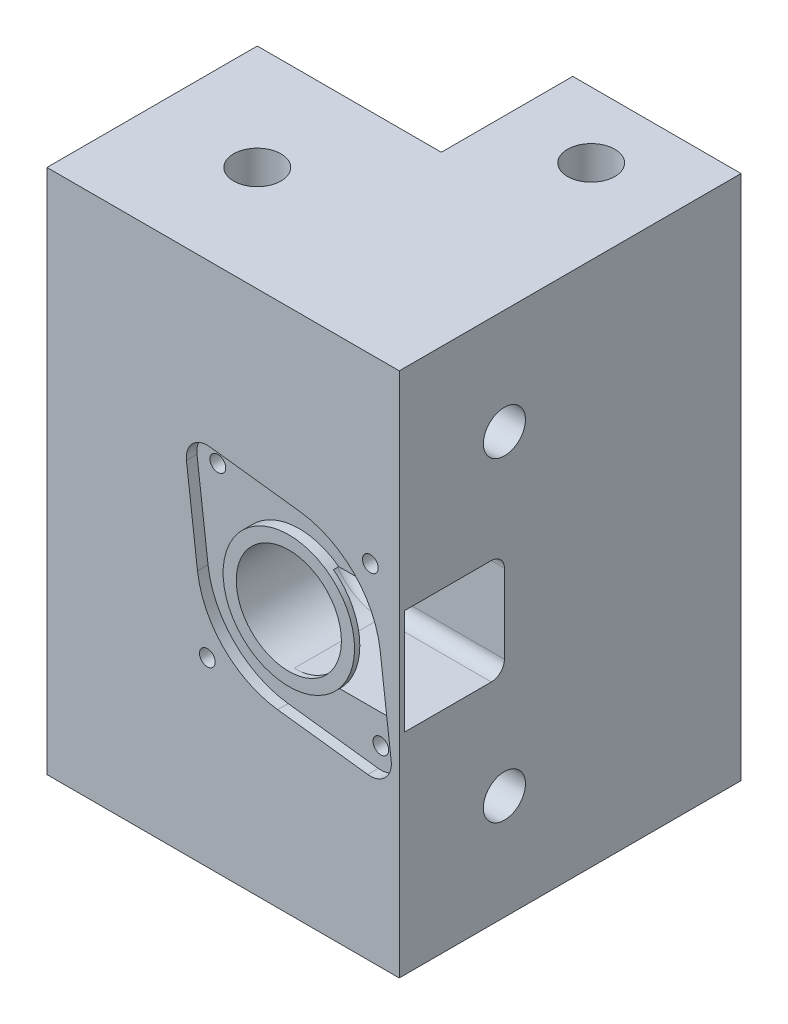
SolidWorks part; units mm, degrees
ref_plane "Front Plane" through (0, 0, 0) normal (0, 0, 1) x (1, 0, 0)
ref_plane "Top Plane" through (0, 0, 0) normal (0, 1, 0) x (1, 0, 0)
ref_plane "Right Plane" through (0, 0, 0) normal (1, 0, 0) x (0, 0, -1)
sketch "Sketch1" plane through (0, 0, 0) normal (0, 1, 0) x (1, 0, 0)
  line L19 (0, -40) -> (0, 0) construction
  line L24 (-25, 0) -> (-5, -40) construction
  line L25 (0, 25) -> (-25, 25) construction
  line L26 (-25, 25) -> (-25, 0) construction
  line L27 (0, 25) -> (32, 0) construction
  line L28 (32, 0) -> (0, 0) construction
  line L29 (-35, 0) -> (0, 0)
  line L30 (-35, -40) -> (-35, 0)
  line L31 (32, -40) -> (-35, -40)
  line L32 (32, 25) -> (32, -40)
  line L33 (0, 25) -> (32, 25)
  line L34 (0, 0) -> (0, 25)
  line L35 (-5, 5) -> (-5, -40) construction
  line L36 (-25, 25) -> (-5, 25) construction
  line L37 (-25, 25) -> (-25, 5) construction
  line L38 (-25, 5) -> (-5, 5) construction
  line L39 (-5, 25) -> (-5, 5) construction
  line L40 (16, 12.5) -> (-5, 22.5) construction
  line L41 (-25, 2.5) -> (-5, 2.5) construction
  line L42 (-25, 2.5) -> (-25, 22.5) construction
  line L43 (-25, 22.5) -> (-5, 22.5) construction
  line L44 (-5, 2.5) -> (-5, 22.5) construction
  line L45 (-25, 2.5) -> (-5, 22.5) construction
  line L46 (-25, 22.5) -> (-5, 2.5) construction
  line L47 (16, 12.5) -> (-5, 2.5) construction
  circle A10 centre (-15, -20) radius 16 construction
  circle A11 centre (-15, -20) radius 6.75 construction
  circle A12 centre (16, 12.5) radius 6 construction
  circle A13 centre (16, 12.5) radius 11 construction
  circle A14 centre (-15, -20) radius 4.5
  circle A15 centre (16, 12.5) radius 4.5
  point P1 (-15, 12.5)
  dimension "D4" = 40
  dimension "D6" = 9
  dimension "D3" = 32
  dimension "D5" = 20
  dimension "D7" = 13.5
  dimension "D8" = 32
  dimension "D9" = 9
  dimension "D10" = 12
  dimension "D11" = 22
  dimension "D1" = 25
  dimension "D2" = 25
  dimension "D12" = 20
extrude "Boss-Extrude1" add sketch "Sketch1" along normal blind 100
sketch "Sketch4" plane through (0, 0, 0) normal (0, -1, 0) x (-1, 0, 0)
  point P0 (15, -20)
hole_wizard "CBORE for M5 Hex Head Bolt2" positions "Sketch4" profile "Sketch5" counterbore size "M5" standard "ANSI Metric"
sketch "Sketch5" plane through (-15, 0, 20) normal (1, 0, 0) x (0, 0, -1)
  line L0 (0, 0) -> (0, 23.85)
  line L1 (0, 23.85) -> (6.75, 23.85)
  line L2 (6.75, 23.85) -> (6.75, 5)
  line L3 (6.75, 5) -> (16, 5)
  line L4 (16, 5) -> (16, 0)
  line L5 (16, 0) -> (0, 0)
  line L10 (0, 23.85) -> (-6.75, 23.85) construction
  line L11 (0, -6.35) -> (0, 107.95) construction
  dimension "Hole Dia." = 13.5
  dimension "Hole Depth" = 23.85
  dimension "C'Bore Dia." = 32
  dimension "C'Bore Depth" = 5
  dimension "Drill Angle" = 180
sketch "Sketch6" plane through (0, 0, 0) normal (0, -1, 0) x (-1, 0, 0)
  point P0 (-16, 12.5)
hole_wizard "CBORE for M5 Hex Head Bolt3" positions "Sketch6" profile "Sketch7" counterbore size "M5" standard "ANSI Metric"
sketch "Sketch7" plane through (16, 0, -12.5) normal (1, 0, 0) x (0, 0, -1)
  line L0 (0, 0) -> (0, 13.5)
  line L1 (0, 13.5) -> (5.1, 13.5)
  line L2 (5.1, 13.5) -> (5.1, 3.5)
  line L3 (5.1, 3.5) -> (11, 3.5)
  line L4 (11, 3.5) -> (11, 0)
  line L5 (11, 0) -> (0, 0)
  line L10 (0, 13.5) -> (-5.1, 13.5) construction
  line L11 (0, -6.35) -> (0, 107.95) construction
  dimension "Hole Dia." = 10.2
  dimension "Hole Depth" = 13.5
  dimension "C'Bore Dia." = 22
  dimension "C'Bore Depth" = 3.5
  dimension "Drill Angle" = 180
sketch "Sketch8" plane through (32, 0, 0) normal (1, 0, 0) x (0, 0, -1)
  line L0 (0, 100) -> (0, 0) construction
  line L1 (-40, 100) -> (25, 100) construction
  line L2 (0, 100) -> (-40, 0) construction
  line L3 (-40, 100) -> (-40, 0) construction
  line L4 (-40, 0) -> (25, 0) construction
  line L5 (-20, 100) -> (-20, 0) construction
  circle A0 centre (-20, 80) radius 4
  circle A1 centre (-20, 20) radius 4
  point P12 (-20, 50)
  point P17 (-20, 21.4284)
  point P18 (0, 0)
  dimension "D1" = 8
  dimension "D2" = 60
  dimension "D3" = 30
extrude "Cut-Extrude1" cut sketch "Sketch8" against normal blind 27
sketch "Sketch9" plane through (0, 0, 40) normal (0, 0, 1) x (1, 0, 0)
  line L0 (-10, 100) -> (-10, 0) construction
  line L2 (-35, 100) -> (32, 100) construction
  line L3 (-35, 0) -> (32, 0) construction
  line L4 (-4.5, 34.5) -> (26.5, 34.5) construction
  line L5 (32, 100) -> (32, 0) construction
  line L6 (32, 100) -> (-10, 0) construction
  line L7 (-4.5, 34.5) -> (-4.5, 65.5) construction
  line L8 (-4.5, 65.5) -> (26.5, 65.5) construction
  line L9 (26.5, 34.5) -> (26.5, 65.5) construction
  line L10 (-4.5, 34.5) -> (26.5, 65.5) construction
  line L11 (-4.5, 65.5) -> (26.5, 34.5) construction
  circle A0 centre (-4.5, 65.5) radius 1.5
  circle A1 centre (26.5, 65.5) radius 1.5
  circle A2 centre (26.5, 34.5) radius 1.5
  circle A3 centre (-4.5, 34.5) radius 1.5
  point P4 (11, 50)
  point P16 (0, 0)
  point P17 (0, 0)
  dimension "D3" = 3
  dimension "D1" = 42
  dimension "D2" = 31
  dimension "D4" = 2
  dimension "D5" = 2
extrude "Cut-Extrude2" cut sketch "Sketch9" against normal blind 119
sketch "Sketch10" plane through (0, 0, 40) normal (0, 0, 1) x (1, 0, 0)
  line L0 (-4.5, 65.5) -> (26.5, 65.5) construction
  line L1 (26.5, 65.5) -> (26.5, 34.5) construction
  line L2 (26.5, 34.5) -> (-4.5, 34.5) construction
  line L3 (-4.5, 34.5) -> (-4.5, 65.5) construction
  line L4 (-4.5, 65.5) -> (26.5, 34.5) construction
  line L5 (26.5, 65.5) -> (-4.5, 34.5) construction
  circle A0 centre (11, 50) radius 10
  dimension "D1" = 20
sketch "Sketch11" plane through (32, 0, 0) normal (1, 0, 0) x (0, 0, -1)
  line L0 (-20, 80) -> (-20, 20) construction
  line L1 (-20, 50) -> (-40, 50) construction
  line L2 (-39, 40) -> (-20, 40)
  line L3 (-39, 40) -> (-39, 60)
  line L4 (-39, 60) -> (-20, 60)
  line L5 (-20, 40) -> (-20, 60)
  line L6 (-39, 40) -> (-20, 60) construction
  line L7 (-39, 60) -> (-20, 40) construction
  line L9 (-40, 60) -> (-40, 40) construction
  line L10 (-40, 65.5) -> (-40, 34.5) construction
  point P4 (-20, 50)
  point P13 (-29.5, 50)
  point P14 (0, 0)
  point P15 (0, 0)
  point P16 (0, 0)
  dimension "D1" = 20
  dimension "D2" = 20
  dimension "D3" = 1
extrude "Cut-Extrude3" cut sketch "Sketch10" against normal blind 20 contours A0
extrude "Cut-Extrude4" cut sketch "Sketch11" against normal blind 21
fillet "Fillet2" radius 2.5 3 edges at (21.5, 40, 20) (1, 50, 20) (21.5, 60, 20)
sketch "Sketch13" plane through (0, 0, 40) normal (0, 0, 1) x (1, 0, 0)
  circle A0 centre (-4.5, 65.5) radius 3
  circle A1 centre (26.5, 65.5) radius 3
  circle A2 centre (26.5, 34.5) radius 3
  circle A3 centre (-4.5, 34.5) radius 3
  dimension "D1" = 6
extrude "Cut-Extrude8" cut sketch "Sketch13" against normal up to next from offset 5 offset against normal yes
sketch "Sketch15" plane through (0, 0, 40) normal (0, 0, 1) x (1, 0, 0)
  line L0 (30.4703, 34.9864) -> (28.3701, 52.1282)
  line L1 (26.0136, 30.5297) -> (8.8718, 32.6299)
  line L2 (-4.0138, 69.4706) -> (13.1284, 67.3701)
  line L3 (-8.4706, 65.0138) -> (-6.3701, 47.8718)
  line L4 (-4.5003, 65.5003) -> (26.5, 34.5) construction
  line L5 (-1.5, 50) -> (23.5, 50) construction
  circle A0 centre (11, 50) radius 12.5
  arc A1 (-6.3701, 47.8718) -> (8.8718, 32.6299) centre (11, 50) ccw
  arc A2 (-4.0138, 69.4706) -> (-8.4706, 65.0138) centre (-4.5003, 65.5003) ccw
  arc A3 (26.0136, 30.5297) -> (30.4703, 34.9864) centre (26.5, 34.5) ccw
  arc A4 (28.3701, 52.1282) -> (13.1284, 67.3701) centre (11, 50) ccw
  point P5 (11, 50)
  point P6 (0, 0)
  dimension "D1" = 25
  dimension "D2" = 17.5
  dimension "D3" = 8
  dimension "D4" = 8
  dimension "D5" = 43.841
  dimension "D6" = 45
  dimension "D7" = 17.1417
  dimension "D8" = 17.1417
  dimension "D9" = 17.142
extrude "Cut-Extrude9" cut sketch "Sketch15" against normal blind 2
